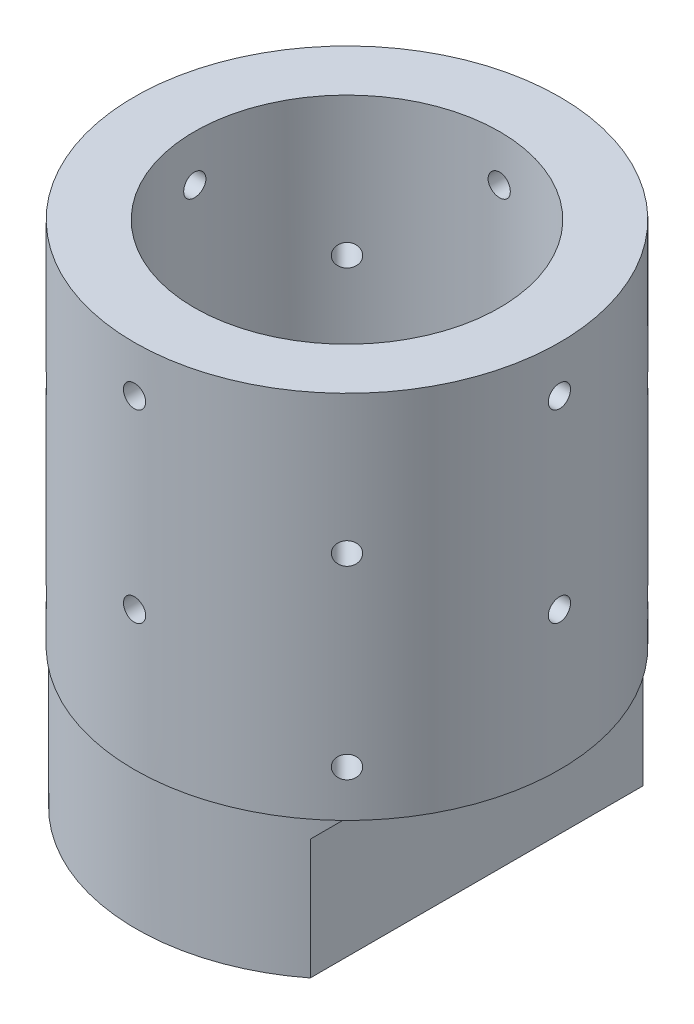
SolidWorks part; units mm, degrees
ref_plane "Спереди" through (0, 0, 0) normal (0, 0, 1) x (1, 0, 0)
ref_plane "Сверху" through (0, 0, 0) normal (0, 1, 0) x (1, 0, 0)
ref_plane "Справа" through (0, 0, 0) normal (1, 0, 0) x (0, 0, -1)
sketch "Эскиз1" plane through (0, 0, 0) normal (0, 1, 0) x (1, 0, 0)
  circle A0 centre (0, 0) radius 23
  dimension "D1" = 46
extrude "Бобышка-Вытянуть1" add sketch "Эскиз1" along normal blind 5
sketch "Эскиз2" plane through (0, 5, 0) normal (0, 1, 0) x (1, 0, 0)
  circle A0 centre (0, 0) radius 23
  circle A1 centre (0, 0) radius 16.5
  circle A2 centre (0, 0) radius 23 construction
  dimension "D1" = 33
  dimension "D2" = 0
extrude "Бобышка-Вытянуть2" add sketch "Эскиз2" along normal blind 35
sketch "Эскиз3" plane through (0, 0, 0) normal (1, 0, 0) x (0, 0, -1)
  line L0 (-23, 20) -> (28.0263, 20) construction
  line L1 (-23, 40) -> (-23, 0) construction
  line L2 (16.5, 40) -> (-16.5, 40) construction
  circle A1 centre (0, 35) radius 1.2
  dimension "D1" = 2.4
  dimension "D2" = 5
extrude "Вырез-Вытянуть1" cut sketch "Эскиз3" against normal through all
ref_plane "Плоскость1" through (0, 0, 0) normal (0.7071, 0, 0.7071) x (0, -1, 0)
sketch "Эскиз4" plane through (0, 0, 0) normal (0.7071, 0, 0.7071) x (0, -1, 0)
  line L0 (-20, 23) -> (-20, -30.0625) construction
  line L1 (0, 23) -> (-40, 23) construction
  line L3 (0, -23) -> (0, 23) construction
  circle A1 centre (-5, 0) radius 1.2
  dimension "D1" = 5
  dimension "D2" = 2.4
extrude "Вырез-Вытянуть2" cut sketch "Эскиз4" against normal through all from offset 16.3 offset against normal yes
pattern_circular "Круговой массив1" count 4 over 360 about axis through (0, 5, 0) along (0, -1, 0) of "Вырез-Вытянуть2"
pattern_circular "Круговой массив2" count 4 over 360 about axis through (0, 5, 0) along (0, -1, 0) of "Вырез-Вытянуть1"
pattern_linear "Линейный массив3" count 2 spacing 20 along (0, 1, 0) of "Круговой массив1"
pattern_linear "Линейный массив4" count 2 spacing 20 along (0, -1, 0) of "Круговой массив2"
sketch "Эскиз12" plane through (0, 0, 0) normal (0, -1, 0) x (1, 0, 0)
  line L1 (14.0272, 18) -> (14.0272, -18)
  line L20 (2.3814, 14.8098) -> (0.0751, 17.9998)
  line L21 (-5.5714, -17.116) -> (-2.3814, -14.8098)
  line L22 (-2.3814, -14.8098) -> (2.3814, 14.8098)
  line L23 (2.3814, 14.8098) -> (0.0751, 17.9998)
  line L24 (-5.5714, -17.116) -> (-2.3814, -14.8098)
  line L25 (-2.3814, -14.8098) -> (2.3814, 14.8098)
  arc A2 (14.0272, 18) -> (14.0272, -18) centre (0, 0) ccw
  arc A13 (0.0751, 17.9998) -> (-5.5714, -17.116) centre (0, 0) ccw
  arc A14 (0.0751, 17.9998) -> (-5.5714, -17.116) centre (0, 0) ccw
  dimension "D1" = 0
extrude "Бобышка-Вытянуть3" add sketch "Эскиз12" along normal blind 15 contours L1 A2 region at (-0.0626, 0, -0.6733)
sketch "Эскиз13" plane through (0, -15, 0) normal (0, -1, 0) x (1, 0, 0)
  line L14 (-5.5186, -17.4481) -> (-2.1049, -14.9801)
  line L15 (2.6973, 14.8848) -> (0.2293, 18.2986)
  line L16 (-2.1049, -14.9801) -> (2.6973, 14.8848)
  line L17 (-5.5186, -17.4481) -> (-2.1049, -14.9801)
  line L18 (2.6973, 14.8848) -> (0.2293, 18.2986)
  line L19 (-2.1049, -14.9801) -> (2.6973, 14.8848)
  arc A5 (0.2293, 18.2986) -> (-5.5186, -17.4481) centre (0, 0) ccw
  arc A6 (0.2293, 18.2986) -> (-5.5186, -17.4481) centre (0, 0) ccw
  dimension "D1" = 0.3
extrude "Вырез-Вытянуть10" cut sketch "Эскиз13" against normal up to surface (15 mm away) up to face at (0, 0, 23)
chamfer "Фаска4" distance 2 angle 45 1 edges at (14.0272, 0, 0)
chamfer "Фаска6" distance 2 angle 45 4 edges at (-3.8118, 0, -16.2141) (-18.0679, 0, 2.9053) (0.2962, 0, -0.0476) (1.4633, 0, 16.5917)
chamfer "Фаска7" distance 2 angle 45 4 edges at (-3.8118, -15, -16.2141) (-18.0679, -15, 2.9053) (1.4633, -15, 16.5917) (0.2962, -15, -0.0476)
